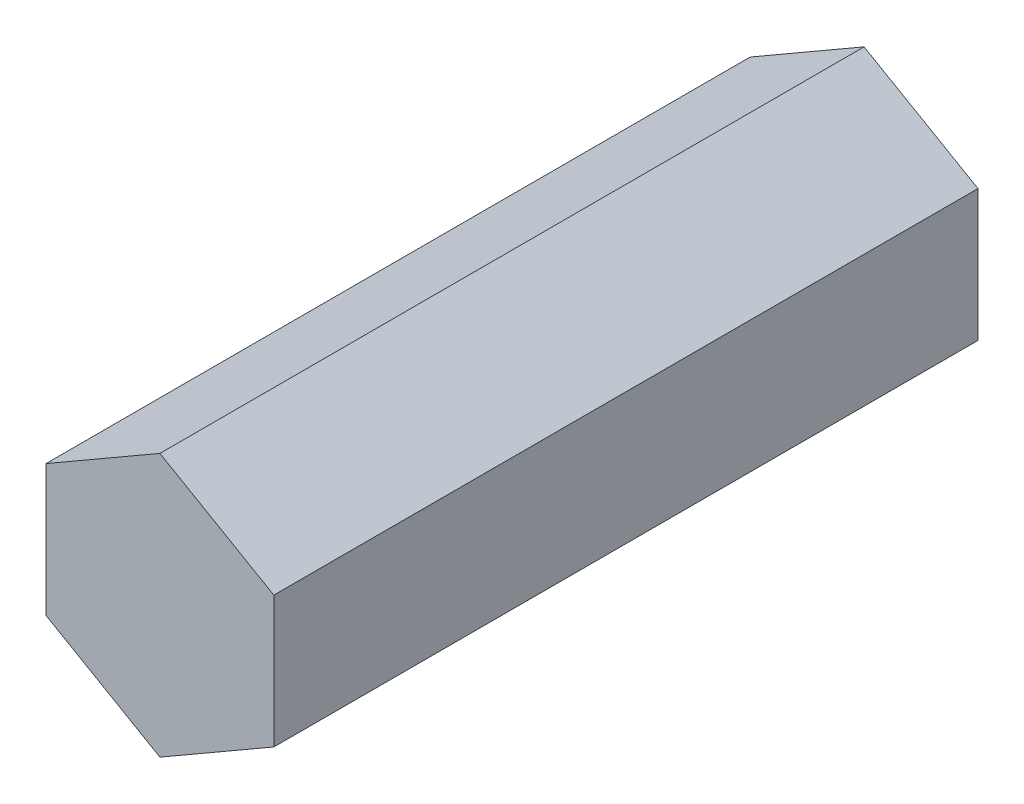
SolidWorks part; units mm, degrees
material "7075-T6 (SN)"
ref_plane "Front Plane" through (0, 0, 0) normal (0, 0, 1) x (1, 0, 0)
ref_plane "Top Plane" through (0, 0, 0) normal (0, 1, 0) x (1, 0, 0)
ref_plane "Right Plane" through (0, 0, 0) normal (1, 0, 0) x (0, 0, -1)
sketch "Sketch1" plane through (0, 0, 0) normal (0, 0, 1) x (1, 0, 0)
  line L1 (0, 7.3323) -> (-6.35, 3.6662)
  line L2 (-6.35, 3.6662) -> (-6.35, -3.6662)
  line L3 (-6.35, -3.6662) -> (0, -7.3323)
  line L4 (0, -7.3323) -> (6.35, -3.6662)
  line L5 (6.35, -3.6662) -> (6.35, 3.6662)
  line L6 (6.35, 3.6662) -> (0, 7.3323)
  circle A0 centre (0, 0) radius 6.35 construction
  point P1 (0, 0)
  dimension "D1" = 12.7
extrude "Boss-Extrude1" add sketch "Sketch1" along normal mid plane 39.2557
